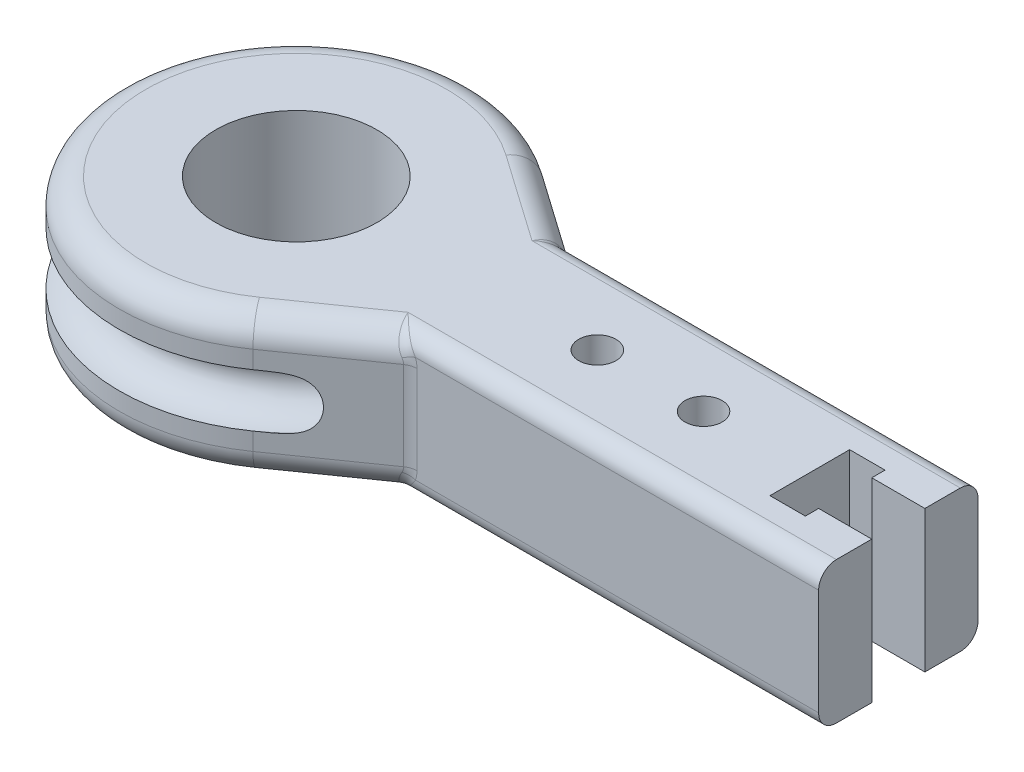
SolidWorks part; units mm, degrees
ref_plane "Front Plane" through (0, 0, 0) normal (0, 0, 1) x (1, 0, 0)
ref_plane "Top Plane" through (0, 0, 0) normal (0, 1, 0) x (1, 0, 0)
ref_plane "Right Plane" through (0, 0, 0) normal (1, 0, 0) x (0, 0, -1)
sketch "Sketch1" plane through (0, 0, 0) normal (0, 1, 0) x (1, 0, 0)
  line L0 (-12.4221, 0) -> (30.45, 0) construction
  line L1 (0, 8.1775) -> (0, -7.8417) construction
  line L2 (11, 4.5) -> (5.7415, 8.1875)
  line L3 (11, -4.5) -> (34, -4.5)
  line L5 (11, 4.5) -> (34, 4.5)
  line L6 (34, -4.5) -> (34, -2.05)
  line L7 (11, -4.5) -> (34, 4.5) construction
  line L8 (11, 4.5) -> (34, -4.5) construction
  line L9 (11, -4.5) -> (5.7415, -8.1875)
  line L10 (11, 4.5) -> (11, -4.5) construction
  line L16 (34, 2.05) -> (34, -2.05)
  line L30 (34, 2.05) -> (34, 4.5)
  arc A0 (5.7415, 8.1875) -> (5.7415, -8.1875) centre (0, 0) ccw
  circle A1 centre (0, 0) radius 4.55
  point P7 (22.5, 0)
  point P20 (-4.55, 0)
  point P48 (34, -2.05)
  dimension "D1" = 20
  dimension "D4" = 9.1
  dimension "D9" = 3.55
  dimension "D2" = 23
  dimension "D3" = 9
extrude "Boss-Extrude2" add sketch "Sketch1" along normal blind 8 contours A1 | L3 L6 L16 L30 L5 L2 A0 L9 region at (0, 0, 0)
sketch "Sketch6" plane through (0, 8, 0) normal (0, 1, 0) x (1, 0, 0)
  line L0 (39.7173, 0) -> (27.2783, 0) construction
  line L2 (34, -4.5) -> (34, 4.5) construction
  line L3 (31, -1.5) -> (34, -1.5)
  line L5 (31, 1.5) -> (34, 1.5)
  line L6 (34, -1.5) -> (34, 1.5)
  line L7 (31, -1.5) -> (34, 1.5) construction
  line L8 (31, 1.5) -> (34, -1.5) construction
  line L9 (31, 1.5) -> (31, 2.25)
  line L10 (29, -2.25) -> (31, -2.25)
  line L11 (29, -2.25) -> (29, 2.25)
  line L12 (29, 2.25) -> (31, 2.25)
  line L13 (31, -2.25) -> (31, -1.5)
  line L14 (29, -2.25) -> (31, 2.25) construction
  line L15 (29, 2.25) -> (31, -2.25) construction
  point P2 (32.5, 0)
  point P11 (30, 0)
  dimension "D1" = 3
  dimension "D2" = 2
  dimension "D3" = 4.5
  dimension "D4" = 3
extrude "Cut-Extrude2" cut sketch "Sketch6" against normal up to next
sketch "Sketch4" plane through (-6.6668, 16.5353, 0) normal (0, 0, 1) x (0, 1, 0)
  line L2 (-8.5353, -12.4083) -> (-8.5353, 3.3332) construction
  line L8 (-16.5353, -6.6668) -> (-4.9826, -6.6668) construction
  line L9 (-8.5353, 3.3332) -> (-16.5353, 3.3332) construction
  ellipse E0 centre (-12.5353, 3.3332) end of major axis (-12.5353, 5.1332) minor radius 1.5 (-14.0353, 3.3332) -> (-11.0353, 3.3332) ccw
  ellipse E1 centre (-12.5353, 3.3332) end of major axis (-11.0353, 3.3332) minor radius 0.4 (-11.0353, 3.3332) -> (-14.0353, 3.3332) ccw
  point P0 (-12.5353, 3.3332)
  point P1 (-12.5353, 3.3332)
  point P4 (0, 0)
  point P13 (-8.5353, 3.3019)
  point P21 (0, 0)
  point P22 (-12.5353, 3.3332)
  point P24 (0, 0)
  dimension "D1" = 1.8
  dimension "D3" = 3
  dimension "D2" = 0.4
fillet "Fillet2" radius 1.5 6 edges at (8.3707, 0, -6.3438) (8.3707, 0, 6.3438) (8.3707, 8, -6.3438) (8.3707, 8, 6.3438) (-10, 0, 0) (-10, 8, 0)
sketch "Sketch5" plane through (0, 8, 0) normal (0, 1, 0) x (1, 0, 0)
  line L0 (11, 6.5426) -> (11, -6.3371) construction
  line L2 (0, 0) -> (39.1502, 0) construction
  line L3 (29, 2.25) -> (29, -2.25) construction
  circle A0 centre (17, 0) radius 1.05
  circle A1 centre (23, 0) radius 1.05
  point P0 (11, -4.5)
  point P1 (11, 4.5)
  point P16 (29, 0)
  dimension "D2" = 2.1
  dimension "D1" = 6
  dimension "D3" = 6
extrude "Cut-Extrude1" cut sketch "Sketch5" against normal blind 10 contours A1 | A0
revolve "Cut-Revolve1" cut sketch "Sketch4" angle 360 about L8
fillet "Fillet3" radius 1 4 edges at (21.1937, 0, -4.5) (21.1937, 0, 4.5) (21.1937, 8, -4.5) (21.1937, 8, 4.5)
fillet "Fillet4" radius 1 5 edges at (10.3282, 7.7361, 4.1769) (10.9624, 6.7537, 4.5) (10.3282, 0.2639, 4.1769) (10.9624, 1.2463, 4.5) (11, 4, 4.5)
fillet "Fillet5" radius 1 5 edges at (10.3282, 0.2639, -4.1769) (10.3282, 7.7361, -4.1769) (10.9624, 1.2463, -4.5) (11, 4, -4.5) (10.9624, 6.7537, -4.5)
